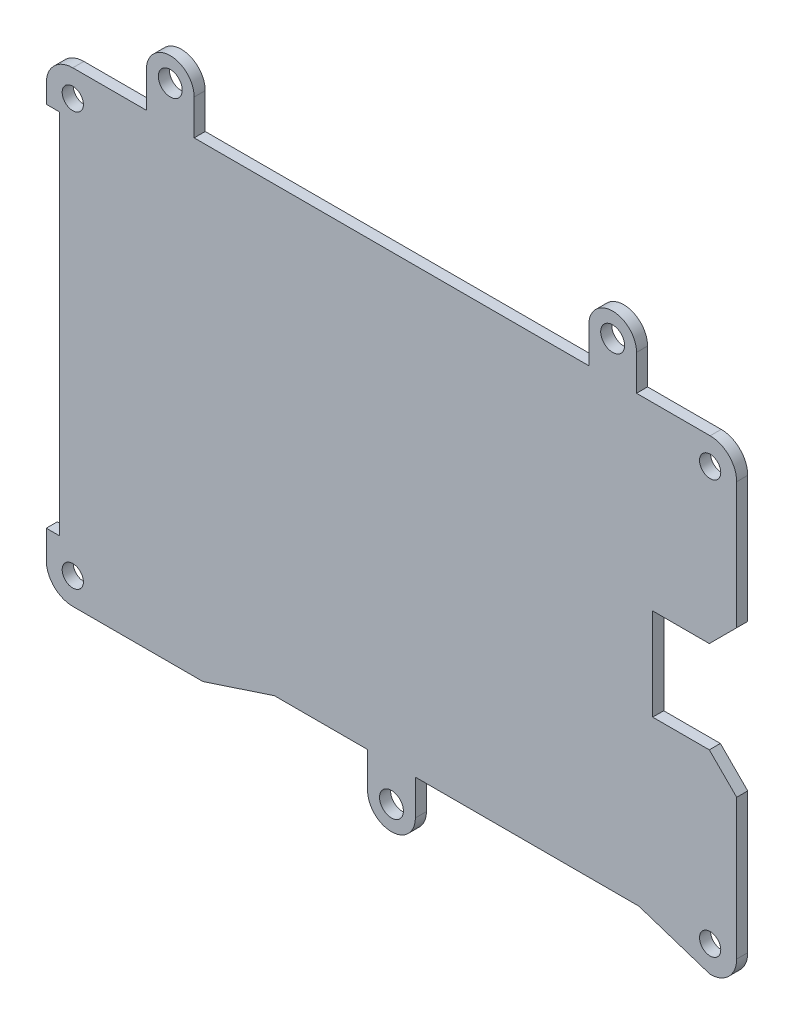
SolidWorks part; units mm, degrees
ref_plane "Front Plane" through (0, 0, 0) normal (0, 0, 1) x (1, 0, 0)
ref_plane "Top Plane" through (0, 0, 0) normal (0, 1, 0) x (1, 0, 0)
ref_plane "Right Plane" through (0, 0, 0) normal (1, 0, 0) x (0, 0, -1)
sketch "Sketch1" plane through (0, 0, 0) normal (0, 0, 1) x (1, 0, 0)
  line L0 (-301.9473, 111.7465) -> (-305.8779, 115.6771) construction
  line L1 (-305.8779, 115.6771) -> (-316.1078, 115.6771) construction
  line L2 (-316.1078, 115.6771) -> (-316.1078, 128.8851) construction
  line L3 (-316.1078, 128.8851) -> (-305.8779, 128.8851) construction
  line L4 (-305.8779, 128.8851) -> (-301.9473, 132.8157) construction
  line L5 (-301.9473, 132.8157) -> (-301.9473, 150.9704) construction
  line L6 (-305.7573, 154.7804) -> (-397.2471, 154.7804) construction
  line L7 (-401.0571, 150.9566) -> (-401.0571, 148.341) construction
  line L8 (-401.0571, 148.341) -> (-399.1521, 148.341) construction
  line L9 (-399.1521, 148.341) -> (-399.1521, 95.6449) construction
  line L10 (-399.1521, 95.6449) -> (-401.0571, 95.6449) construction
  line L11 (-401.0571, 95.6449) -> (-401.0571, 91.6593) construction
  line L12 (-397.2472, 87.8217) -> (-378.5565, 87.8217) construction
  line L13 (-378.5565, 87.8217) -> (-368.3165, 91.1883) construction
  line L14 (-368.3165, 91.1883) -> (-315.9973, 91.1883) construction
  line L15 (-315.9973, 91.1883) -> (-305.7573, 87.8217) construction
  line L16 (-301.9473, 91.6317) -> (-301.9473, 111.7465) construction
  line L17 (-301.9473, 111.7465) -> (-305.8779, 115.6771)
  line L18 (-305.8779, 115.6771) -> (-316.1078, 115.6771)
  line L19 (-316.1078, 115.6771) -> (-316.1078, 128.8851)
  line L20 (-316.1078, 128.8851) -> (-305.8779, 128.8851)
  line L21 (-305.8779, 128.8851) -> (-301.9473, 132.8157)
  line L22 (-301.9473, 132.8157) -> (-301.9473, 150.9704)
  line L23 (-305.7573, 154.7804) -> (-397.2471, 154.7804)
  line L24 (-401.0571, 150.9566) -> (-401.0571, 148.341)
  line L25 (-401.0571, 148.341) -> (-399.1521, 148.341)
  line L26 (-399.1521, 148.341) -> (-399.1521, 95.6449)
  line L27 (-399.1521, 95.6449) -> (-401.0571, 95.6449)
  line L28 (-401.0571, 95.6449) -> (-401.0571, 91.6593)
  line L29 (-397.2472, 87.8217) -> (-378.5565, 87.8217)
  line L30 (-378.5565, 87.8217) -> (-368.3165, 91.1883)
  line L31 (-368.3165, 91.1883) -> (-315.9973, 91.1883)
  line L32 (-315.9973, 91.1883) -> (-305.7573, 87.8217)
  line L33 (-301.9473, 91.6317) -> (-301.9473, 111.7465)
  circle A0 centre (-305.7573, 91.6317) radius 1.3559 construction
  circle A1 centre (-305.7573, 150.9704) radius 1.3559 construction
  circle A2 centre (-397.2471, 150.9704) radius 1.3559 construction
  circle A3 centre (-397.2472, 91.6317) radius 1.3559 construction
  circle A4 centre (-305.7573, 91.6317) radius 1.3559
  circle A5 centre (-305.7573, 150.9704) radius 1.3559
  circle A6 centre (-397.2471, 150.9704) radius 1.3559
  circle A7 centre (-397.2472, 91.6317) radius 1.3559
  arc A8 (-301.9473, 150.9704) -> (-305.7573, 154.7804) centre (-305.7573, 150.9704) ccw construction
  arc A9 (-397.2471, 154.7804) -> (-401.0571, 150.9566) centre (-397.2471, 150.9704) ccw construction
  arc A10 (-401.0571, 91.6593) -> (-397.2472, 87.8217) centre (-397.2472, 91.6317) ccw construction
  arc A11 (-305.7573, 87.8217) -> (-301.9473, 91.6317) centre (-305.7573, 91.6317) ccw construction
  arc A12 (-301.9473, 150.9704) -> (-305.7573, 154.7804) centre (-305.7573, 150.9704) ccw
  arc A13 (-397.2471, 154.7804) -> (-401.0571, 150.9566) centre (-397.2471, 150.9704) ccw
  arc A14 (-401.0571, 91.6593) -> (-397.2472, 87.8217) centre (-397.2472, 91.6317) ccw
  arc A15 (-305.7573, 87.8217) -> (-301.9473, 91.6317) centre (-305.7573, 91.6317) ccw
extrude "Boss-Extrude1" add sketch "Sketch1" along normal blind 1.5875
sketch "Sketch2" plane through (0, 0, 1.5875) normal (0, 0, 1) x (1, 0, 0)
  line L0 (-351.5022, 121.301) -> (-351.5022, 159.401) construction
  line L1 (-301.9473, 150.9704) -> (-301.9473, 91.6317) construction
  line L2 (-401.0571, 121.301) -> (-301.9473, 121.301) construction
  line L3 (-351.5022, 83.201) -> (-351.5022, 159.401) construction
  line L4 (-361.0272, 83.201) -> (-361.0272, 159.401)
  line L5 (-341.9772, 83.201) -> (-341.9772, 159.401)
  line L6 (-361.0272, 154.7804) -> (-341.9772, 154.7804)
  line L7 (-305.7573, 154.7804) -> (-397.2471, 154.7804) construction
  line L8 (-361.0272, 91.6317) -> (-341.9772, 91.6317)
  circle A0 centre (-351.5022, 159.401) radius 3.175
  arc A1 (-361.0272, 83.201) -> (-341.9772, 83.201) centre (-351.5022, 83.201) ccw
  arc A2 (-341.9772, 159.401) -> (-361.0272, 159.401) centre (-351.5022, 159.401) ccw
  circle A3 centre (-351.5022, 83.201) radius 3.175
  point P13 (-351.5022, 121.301)
  line M11 (-305.7573, 154.7804) -> (-397.2471, 154.7804)
  line M21 (-368.3165, 91.1883) -> (-315.9973, 91.1883)
  dimension "D1" = 6.35
  dimension "D2" = 38.1
  dimension "D3" = 19.05
extrude "Boss-Extrude2" [suppressed] add sketch "Sketch2" against normal blind 1.5875 contours L5 A2 L4 A0 M11 | L4 A1 L5 A3 M21
sketch "Sketch3" plane through (0, 0, 1.5875) normal (0, 0, 1) x (1, 0, 0)
  circle A0 centre (-397.2471, 150.9704) radius 1.524
  circle A1 centre (-305.7573, 150.9704) radius 1.524
  circle A2 centre (-305.7573, 91.6317) radius 1.524
  circle A3 centre (-397.2472, 91.6317) radius 1.524
  dimension "D1" = 3.048
extrude "Cut-Extrude1" cut sketch "Sketch3" against normal through all
sketch "Sketch4" plane through (0, 0, 1.5875) normal (0, 0, 1) x (1, 0, 0)
  line L0 (-301.9473, 132.8157) -> (-305.8779, 128.8851)
  line L1 (-301.9473, 132.8157) -> (-301.9473, 150.9704) construction
  line L2 (-305.8779, 128.8851) -> (-314.0048, 128.8851)
  line L3 (-314.0048, 128.8851) -> (-314.0048, 115.6771)
  line L4 (-314.0048, 115.6771) -> (-305.8779, 115.6771)
  line L5 (-305.8779, 115.6771) -> (-301.9473, 111.7465)
  line L6 (-301.9473, 91.6317) -> (-301.9473, 111.7465) construction
  line L7 (-301.9473, 132.8157) -> (-301.9473, 111.7465)
  line L8 (-301.9473, 111.7465) -> (-305.8779, 115.6771) construction
  line L9 (-305.8779, 115.6771) -> (-316.1078, 115.6771) construction
  line L10 (-316.1078, 128.8851) -> (-305.8779, 128.8851) construction
  dimension "D1" = 12.0575
sketch "Sketch5" plane through (0, 0, 1.5875) normal (0, 0, 1) x (1, 0, 0)
  line L1 (-314.0048, 128.8851) -> (-316.1078, 128.8851)
  line L2 (-314.0048, 128.8851) -> (-314.0048, 115.6771)
  line L3 (-314.0048, 115.6771) -> (-316.1078, 115.6771)
  line L4 (-316.1078, 128.8851) -> (-316.1078, 115.6771)
extrude "Boss-Extrude3" add sketch "Sketch5" against normal up to vertex (1.5875 mm away) up to point (-316.1078, 128.8851, 0)
sketch "Sketch6" plane through (0, 0, 1.5875) normal (0, 0, 1) x (1, 0, 0)
  line L0 (-386.6812, 159.8604) -> (-386.6812, 154.7804)
  line L1 (-305.7573, 154.7804) -> (-397.2471, 154.7804) construction
  line L2 (-379.8232, 159.8604) -> (-379.8232, 154.7804)
  line L3 (-379.8232, 154.7804) -> (-386.6812, 154.7804)
  line L4 (-316.3232, 159.8604) -> (-316.3232, 154.7804)
  line L5 (-316.3232, 154.7804) -> (-323.1812, 154.7804)
  line L6 (-323.1812, 154.7804) -> (-323.1812, 159.8604)
  line L7 (-383.2522, 159.8604) -> (-319.7522, 159.8604) construction
  line L8 (-351.5022, 159.8604) -> (-351.5022, 154.7804) construction
  line L10 (-351.5022, 154.7804) -> (-351.5022, 91.1883) construction
  line L11 (-368.3165, 91.1883) -> (-315.9973, 91.1883) construction
  line L12 (-354.9312, 86.1083) -> (-354.9312, 91.1883)
  line L13 (-354.9312, 91.1883) -> (-348.0732, 91.1883)
  line L14 (-348.0732, 91.1883) -> (-348.0732, 86.1083)
  circle A0 centre (-383.2522, 159.8604) radius 1.7145
  circle A1 centre (-319.7522, 159.8604) radius 1.7145
  circle A2 centre (-383.2522, 159.8604) radius 3.429
  circle A3 centre (-319.7522, 159.8604) radius 3.429
  circle A4 centre (-351.5022, 86.1083) radius 1.7145
  circle A5 centre (-351.5022, 86.1083) radius 3.429
  line M7 (-305.7573, 154.7804) -> (-397.2471, 154.7804)
  line M17 (-368.3165, 91.1883) -> (-315.9973, 91.1883)
  dimension "D2" = 6.858
  dimension "D3" = 3.429
  dimension "D4" = 5.08
  dimension "D5" = 6.858
  dimension "D6" = 3.429
  dimension "D7" = 5.08
  dimension "D1" = 63.5
extrude "Boss-Extrude4" add sketch "Sketch6" against normal up to vertex (1.5875 mm away) contours A2 A0 | A2 L0 L2 M7 | A3 L6 L4 M7 | A3 A1 | A5 A4 | A5 L14 L12 M17 region at (-383.2522, 156.0965, 1.5875) region at (-319.7522, 156.0965, 1.5875) region at (-383.2522, 163.1924, 1.5875) region at (-319.7522, 163.1924, 1.5875) region at (-351.5022, 89.8722, 1.5875) region at (-351.5022, 89.4403, 1.5875) up to point (-368.3165, 91.1883, 0)
